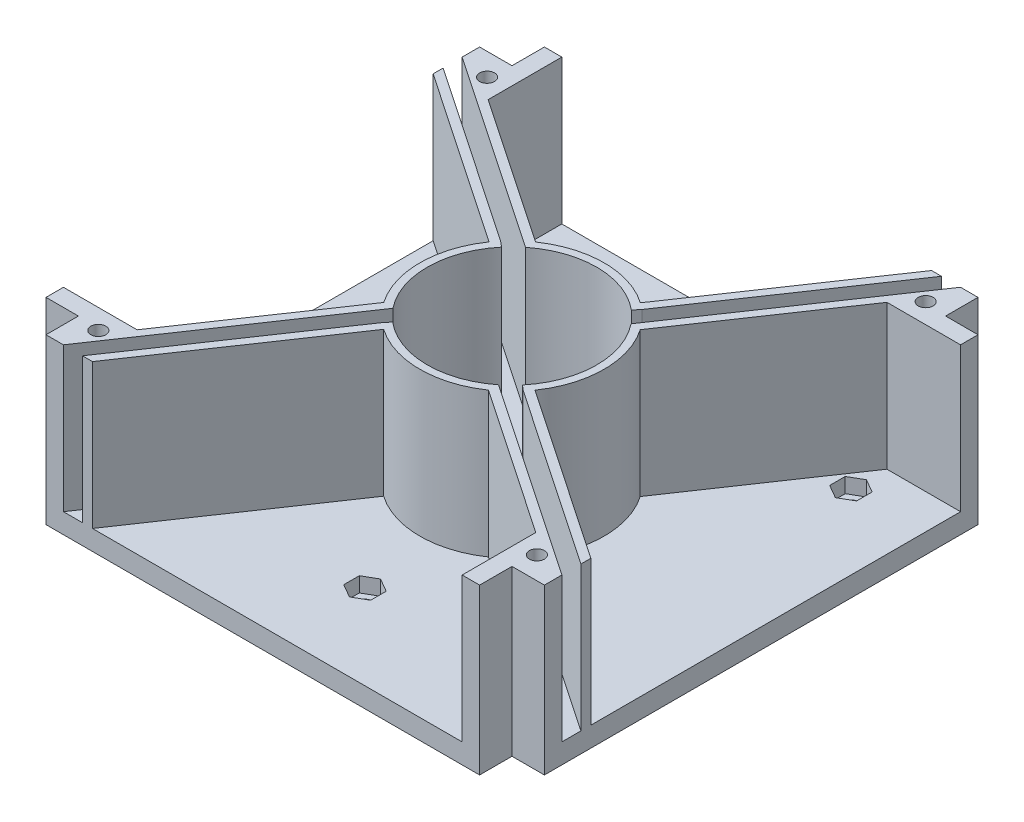
SolidWorks part; units mm, degrees
ref_plane "Front Plane" through (0, 0, 0) normal (0, 0, 1) x (1, 0, 0)
ref_plane "Top Plane" through (0, 0, 0) normal (0, 1, 0) x (1, 0, 0)
ref_plane "Right Plane" through (0, 0, 0) normal (1, 0, 0) x (0, 0, -1)
sketch "Sketch1" plane through (0, 0, 0) normal (0, 1, 0) x (1, 0, 0)
  line L0 (0, -50) -> (0, 50) construction
  line L1 (-50, 0) -> (50, 0) construction
  line L2 (-55, 0) -> (55, 0) construction
  line L3 (0, -55) -> (0, 55) construction
  line L5 (50, 50) -> (-50, 50)
  line L6 (50, 50) -> (50, -50)
  line L7 (50, -50) -> (-50, -50)
  line L8 (-50, 50) -> (-50, -50)
  point P10 (0, 0)
extrude "Boss-Extrude1" add sketch "Sketch1" along normal blind 4
sketch "Sketch2" plane through (0, 4, 0) normal (0, 1, 0) x (1, 0, 0)
  circle A0 centre (0, 0) radius 4.7625
extrude "Cut-Extrude1" cut sketch "Sketch2" against normal through all contours A0
sketch "Sketch3" plane through (0, 4, 0) normal (0, 1, 0) x (1, 0, 0)
  line L0 (0, -2.2) -> (0, 2.2) construction
  line L1 (-50, 50) -> (-41.5, 50)
  line L2 (-50, 50) -> (-50, 41.5)
  line L3 (-50, 41.5) -> (-41.5, 41.5)
  line L4 (-41.5, 50) -> (-41.5, 41.5)
  line L5 (50, 41.5) -> (41.5, 41.5)
  line L6 (41.5, 50) -> (41.5, 41.5)
  line L7 (50, 50) -> (41.5, 50)
  line L8 (50, 50) -> (50, 41.5)
  line L9 (-2.2, 0) -> (2.2, 0) construction
  line L10 (50, -50) -> (50, -41.5)
  line L11 (50, -50) -> (41.5, -50)
  line L12 (41.5, -50) -> (41.5, -41.5)
  line L13 (50, -41.5) -> (41.5, -41.5)
  line L14 (-50, -41.5) -> (-41.5, -41.5)
  line L15 (-41.5, -50) -> (-41.5, -41.5)
  line L16 (-50, -50) -> (-41.5, -50)
  line L17 (-50, -50) -> (-50, -41.5)
extrude "Cut-Extrude2" cut sketch "Sketch3" against normal through all
sketch "Sketch4" plane through (0, 4, 0) normal (0, 1, 0) x (1, 0, 0)
  line L0 (0, -2.2) -> (0, 2.2) construction
  line L1 (-10.9274, -13.0228) -> (-11.8916, -14.1718)
  line L2 (10.9274, -13.0228) -> (11.8916, -14.1718)
  line L3 (-13.0228, -10.9274) -> (-14.1718, -11.8916)
  line L4 (-13.0228, 10.9274) -> (-14.1718, 11.8916)
  line L5 (-10.9274, 13.0228) -> (-11.8916, 14.1718)
  line L6 (10.9274, 13.0228) -> (11.8916, 14.1718)
  line L7 (13.0228, 10.9274) -> (14.1718, 11.8916)
  line L8 (13.0228, -10.9274) -> (14.1718, -11.8916)
  line L9 (0, 0) -> (0, -17) construction
  circle A0 centre (0, 0) radius 17 construction
  arc A2 (-10.9274, -13.0228) -> (10.9274, -13.0228) centre (0, 0) ccw
  arc A3 (-11.8916, -14.1718) -> (11.8916, -14.1718) centre (0, 0) ccw
  arc A4 (-13.0228, 10.9274) -> (-13.0228, -10.9274) centre (0, 0) ccw
  arc A5 (-14.1718, 11.8916) -> (-14.1718, -11.8916) centre (0, 0) ccw
  arc A6 (10.9274, 13.0228) -> (-10.9274, 13.0228) centre (0, 0) ccw
  arc A7 (11.8916, 14.1718) -> (-11.8916, 14.1718) centre (0, 0) ccw
  arc A8 (13.0228, -10.9274) -> (13.0228, 10.9274) centre (0, 0) ccw
  arc A9 (14.1718, -11.8916) -> (14.1718, 11.8916) centre (0, 0) ccw
  dimension "D1" = 4
  dimension "D2" = 17
extrude "Boss-Extrude3" add sketch "Sketch4" along normal blind 29
sketch "Sketch7" plane through (0, 4, 0) normal (0, 1, 0) x (1, 0, 0)
  line L0 (-41.5, -41.5) -> (-41.5, -50)
  line L1 (-41.5, -50) -> (-40, -50)
  line L2 (-41.5, -50) -> (41.5, -50) construction
  line L3 (-41.5, -41.5) -> (-50, -41.5)
  line L4 (-50, -41.5) -> (-50, -40)
  line L5 (-50, 41.5) -> (-50, -41.5) construction
  line L6 (-40, -50) -> (-40, -40)
  line L7 (-40, -40) -> (-50, -40)
  line L8 (0, -18.15) -> (0, 18.15) construction
  line L9 (40, -50) -> (40, -40)
  line L10 (50, -41.5) -> (50, -40)
  line L11 (41.5, -41.5) -> (50, -41.5)
  line L12 (41.5, -41.5) -> (41.5, -50)
  line L13 (41.5, -50) -> (40, -50)
  line L14 (40, -40) -> (50, -40)
  line L15 (-18.15, 0) -> (18.15, 0) construction
  line L16 (50, 41.5) -> (50, 40)
  line L17 (40, 50) -> (40, 40)
  line L18 (40, 40) -> (50, 40)
  line L19 (41.5, 41.5) -> (50, 41.5)
  line L20 (41.5, 50) -> (40, 50)
  line L21 (41.5, 41.5) -> (41.5, 50)
  line L22 (-50, 41.5) -> (-50, 40)
  line L23 (-41.5, 41.5) -> (-50, 41.5)
  line L24 (-40, 40) -> (-50, 40)
  line L25 (-40, 50) -> (-40, 40)
  line L26 (-41.5, 50) -> (-40, 50)
  line L27 (-41.5, 41.5) -> (-41.5, 50)
extrude "Boss-Extrude4" add sketch "Sketch7" along normal blind 29
sketch "Sketch8" plane through (0, 4, 0) normal (0, 1, 0) x (1, 0, 0)
  line L11 (-14.1718, -11.8916) -> (-40, -50)
  line L12 (-11.8916, -14.1718) -> (-36.1743, -50)
  line L13 (-40, -50) -> (40, -50) construction
  line L14 (-36.1743, -50) -> (-40, -50)
  line L15 (-14.1718, -11.8916) -> (-12.4887, -9.4082)
  line L16 (-11.8916, -14.1718) -> (-9.8672, -11.1849)
  line L17 (-9.8672, -11.1849) -> (-12.4887, -9.4082)
  line L18 (-11.8916, 14.1718) -> (-50, 40)
  line L19 (-14.1718, 11.8916) -> (-50, 36.1743)
  line L20 (-50, 40) -> (-50, -40) construction
  line L21 (-50, 40) -> (-50, 36.1743)
  line L22 (-11.8916, 14.1718) -> (-9.4082, 12.4887)
  line L23 (-14.1718, 11.8916) -> (-11.1849, 9.8672)
  line L24 (-11.1849, 9.8672) -> (-9.4082, 12.4887)
  line L25 (14.1718, 11.8916) -> (40, 50)
  line L26 (11.8916, 14.1718) -> (36.1743, 50)
  line L27 (40, 50) -> (-40, 50) construction
  line L28 (36.1743, 50) -> (40, 50)
  line L29 (14.1718, 11.8916) -> (12.4887, 9.4082)
  line L30 (11.8916, 14.1718) -> (9.8672, 11.1849)
  line L31 (9.8672, 11.1849) -> (12.4887, 9.4082)
  line L32 (11.8916, -14.1718) -> (50, -40)
  line L33 (14.1718, -11.8916) -> (50, -36.1743)
  line L34 (50, -40) -> (50, 40) construction
  line L35 (50, -36.1743) -> (50, -40)
  line L36 (11.8916, -14.1718) -> (9.4082, -12.4887)
  line L37 (14.1718, -11.8916) -> (11.1849, -9.8672)
  line L38 (11.1849, -9.8672) -> (9.4082, -12.4887)
extrude "Cut-Extrude4" cut sketch "Sketch8" along normal through all
sketch "Sketch9" plane through (0, 4, 0) normal (0, 1, 0) x (1, 0, 0)
  line L0 (-11.8916, -14.1718) -> (-36.1743, -50)
  line L1 (-36.1743, -50) -> (-34.1743, -50)
  line L2 (-40, -50) -> (40, -50) construction
  line L5 (-14.1718, -11.8916) -> (-40, -50)
  line L6 (-34.1743, -50) -> (-10.5211, -15.1007)
  line L7 (-10.5211, -15.1007) -> (-11.8916, -14.1718)
  line L8 (-40, -50) -> (-42, -50) construction
  line L9 (-42, -50) -> (-40, -47.0491) construction
  line L10 (-40, -50) -> (-40, -40) construction
  line L11 (-40, -47.0491) -> (-14.9813, -10.1349)
  line L12 (-14.9813, -10.1349) -> (-13.6108, -11.0638)
  line L13 (-14.1718, -11.8916) -> (-12.4887, -9.4082) construction
  line L14 (-13.6108, -11.0638) -> (-14.1718, -11.8916)
  line L15 (-40, -47.0491) -> (-40, -50)
  line L16 (-50, 34.1743) -> (-15.1007, 10.5211)
  line L17 (-50, 36.1743) -> (-50, 34.1743)
  line L18 (-14.1718, 11.8916) -> (-50, 36.1743)
  line L19 (-11.8916, 14.1718) -> (-50, 40)
  line L20 (-47.0491, 40) -> (-10.1349, 14.9813)
  line L21 (-15.1007, 10.5211) -> (-14.1718, 11.8916)
  line L22 (-11.0638, 13.6108) -> (-11.8916, 14.1718)
  line L23 (-10.1349, 14.9813) -> (-11.0638, 13.6108)
  line L24 (-50, 42) -> (-47.0491, 40) construction
  line L25 (-50, 40) -> (-50, 42) construction
  line L26 (-47.0491, 40) -> (-50, 40)
  line L27 (34.1743, 50) -> (10.5211, 15.1007)
  line L28 (36.1743, 50) -> (34.1743, 50)
  line L29 (11.8916, 14.1718) -> (36.1743, 50)
  line L30 (14.1718, 11.8916) -> (40, 50)
  line L31 (40, 47.0491) -> (14.9813, 10.1349)
  line L32 (10.5211, 15.1007) -> (11.8916, 14.1718)
  line L33 (13.6108, 11.0638) -> (14.1718, 11.8916)
  line L34 (14.9813, 10.1349) -> (13.6108, 11.0638)
  line L35 (42, 50) -> (40, 47.0491) construction
  line L36 (40, 50) -> (42, 50) construction
  line L37 (40, 47.0491) -> (40, 50)
  line L38 (50, -34.1743) -> (15.1007, -10.5211)
  line L39 (50, -36.1743) -> (50, -34.1743)
  line L40 (14.1718, -11.8916) -> (50, -36.1743)
  line L41 (11.8916, -14.1718) -> (50, -40)
  line L42 (47.0491, -40) -> (10.1349, -14.9813)
  line L43 (15.1007, -10.5211) -> (14.1718, -11.8916)
  line L44 (11.0638, -13.6108) -> (11.8916, -14.1718)
  line L45 (10.1349, -14.9813) -> (11.0638, -13.6108)
  line L46 (50, -42) -> (47.0491, -40) construction
  line L47 (50, -40) -> (50, -42) construction
  line L48 (47.0491, -40) -> (50, -40)
  dimension "D1" = 1.6556
  dimension "D2" = 1.6556
  dimension "D3" = 4
extrude "Boss-Extrude5" add sketch "Sketch9" along normal blind 29
sketch "Sketch11" plane through (0, 4, 0) normal (0, 1, 0) x (1, 0, 0)
  line L0 (-40, -40) -> (-35.2225, -40)
  line L1 (-15.2301, -10.5021) -> (-40, -47.0491) construction
  line L2 (-35.2225, -40) -> (-40, -47.0491)
  line L3 (-40, -47.0491) -> (-40, -40)
  line L4 (-40, 40) -> (-40, 35.2225)
  line L5 (-47.0491, 40) -> (-40, 40)
  line L6 (-40, 35.2225) -> (-47.0491, 40)
  line L7 (40, 40) -> (35.2225, 40)
  line L8 (40, 47.0491) -> (40, 40)
  line L9 (35.2225, 40) -> (40, 47.0491)
  line L10 (40, -40) -> (40, -35.2225)
  line L11 (47.0491, -40) -> (40, -40)
  line L12 (40, -35.2225) -> (47.0491, -40)
  dimension "D1" = 4
extrude "Boss-Extrude6" add sketch "Sketch11" along normal blind 29
sketch "Sketch12" plane through (0, 0, 0) normal (0, -1, 0) x (-1, 0, 0)
  line L0 (0, 0) -> (-3.5, 0) construction
  line L1 (-3.5, 0) -> (-3.5, 33) construction
  line L2 (-3.5, 33) -> (-35, 33) construction
  line L3 (-18.15, 0) -> (18.15, 0) construction
  line L4 (-3.5, 0) -> (-3.5, -33) construction
  line L5 (-35, 33) -> (-35, -33) construction
  line L6 (-35, -33) -> (-28, -33) construction
  circle A0 centre (-3.5, 33) radius 1.5
  circle A3 centre (-3.5, -33) radius 1.5
  circle A6 centre (-35, 33) radius 1.5
  circle A7 centre (-28, -33) radius 1.5
extrude "Cut-Extrude5" cut sketch "Sketch12" against normal through all contours A0 | A6 | A3 | A7
sketch "Sketch14" plane through (0, 4, 0) normal (0, 1, 0) x (1, 0, 0)
  line L1 (28, -29.8823) -> (25.3, -31.4412)
  line L2 (25.3, -31.4412) -> (25.3, -34.5588)
  line L3 (25.3, -34.5588) -> (28, -36.1177)
  line L4 (28, -36.1177) -> (30.7, -34.5588)
  line L5 (30.7, -34.5588) -> (30.7, -31.4412)
  line L6 (30.7, -31.4412) -> (28, -29.8823)
  line L7 (3.5, -29.8823) -> (0.8, -31.4412)
  line L8 (0.8, -31.4412) -> (0.8, -34.5588)
  line L9 (0.8, -34.5588) -> (3.5, -36.1177)
  line L10 (3.5, -36.1177) -> (6.2, -34.5588)
  line L11 (6.2, -34.5588) -> (6.2, -31.4412)
  line L12 (6.2, -31.4412) -> (3.5, -29.8823)
  line L13 (3.5, 36.1177) -> (0.8, 34.5588)
  line L14 (0.8, 34.5588) -> (0.8, 31.4412)
  line L15 (0.8, 31.4412) -> (3.5, 29.8823)
  line L16 (3.5, 29.8823) -> (6.2, 31.4412)
  line L17 (6.2, 31.4412) -> (6.2, 34.5588)
  line L18 (6.2, 34.5588) -> (3.5, 36.1177)
  line L19 (35, 36.1177) -> (32.3, 34.5588)
  line L20 (32.3, 34.5588) -> (32.3, 31.4412)
  line L21 (32.3, 31.4412) -> (35, 29.8823)
  line L22 (35, 29.8823) -> (37.7, 31.4412)
  line L23 (37.7, 31.4412) -> (37.7, 34.5588)
  line L24 (37.7, 34.5588) -> (35, 36.1177)
  circle A0 centre (28, -33) radius 2.7 construction
  circle A1 centre (3.5, -33) radius 2.7 construction
  circle A2 centre (3.5, 33) radius 2.7 construction
  circle A3 centre (35, 33) radius 2.7 construction
extrude "Cut-Extrude6" cut sketch "Sketch14" against normal blind 3
sketch "Sketch15" plane through (0, 33, 0) normal (0, 1, 0) x (1, 0, 0)
  line L0 (41.5, -41.5) -> (41.5, -39) construction
  line L1 (41.5, -39) -> (44, -39) construction
  circle A0 centre (44, -39) radius 1.5
  circle A1 centre (-39, -44) radius 1.5
  circle A2 centre (-44, 39) radius 1.5
  circle A3 centre (39, 44) radius 1.5
  dimension "D1" = 4
extrude "Cut-Extrude7" cut sketch "Sketch15" against normal blind 10
sketch "Sketch16" plane through (0, 0, 0) normal (0, -1, 0) x (1, 0, 0)
  line L0 (-50, 41.5) -> (-50, 43.5)
  line L1 (-41.5, 50) -> (-43.5, 50)
  line L2 (-50, 43.5) -> (-43.5, 43.5)
  line L3 (-43.5, 43.5) -> (-43.5, 50)
  line L4 (-50, 41.5) -> (-41.5, 41.5)
  line L5 (-41.5, 41.5) -> (-41.5, 50)
  line L6 (0, -18.15) -> (0, 18.15) construction
  line L7 (50, 41.5) -> (41.5, 41.5)
  line L8 (50, 41.5) -> (50, 43.5)
  line L9 (50, 43.5) -> (43.5, 43.5)
  line L10 (43.5, 43.5) -> (43.5, 50)
  line L11 (41.5, 50) -> (43.5, 50)
  line L12 (41.5, 41.5) -> (41.5, 50)
  line L13 (18.15, 0) -> (-18.15, 0) construction
  line L14 (50, -41.5) -> (50, -43.5)
  line L15 (50, -43.5) -> (43.5, -43.5)
  line L16 (43.5, -43.5) -> (43.5, -50)
  line L17 (41.5, -50) -> (43.5, -50)
  line L18 (41.5, -41.5) -> (41.5, -50)
  line L19 (50, -41.5) -> (41.5, -41.5)
  line L20 (-50, -41.5) -> (-41.5, -41.5)
  line L21 (-50, -41.5) -> (-50, -43.5)
  line L22 (-50, -43.5) -> (-43.5, -43.5)
  line L23 (-43.5, -43.5) -> (-43.5, -50)
  line L24 (-41.5, -50) -> (-43.5, -50)
  line L25 (-41.5, -41.5) -> (-41.5, -50)
extrude "Boss-Extrude7" add sketch "Sketch16" against normal up to surface (33 mm away) up to face at (44, 33, 40.5)
